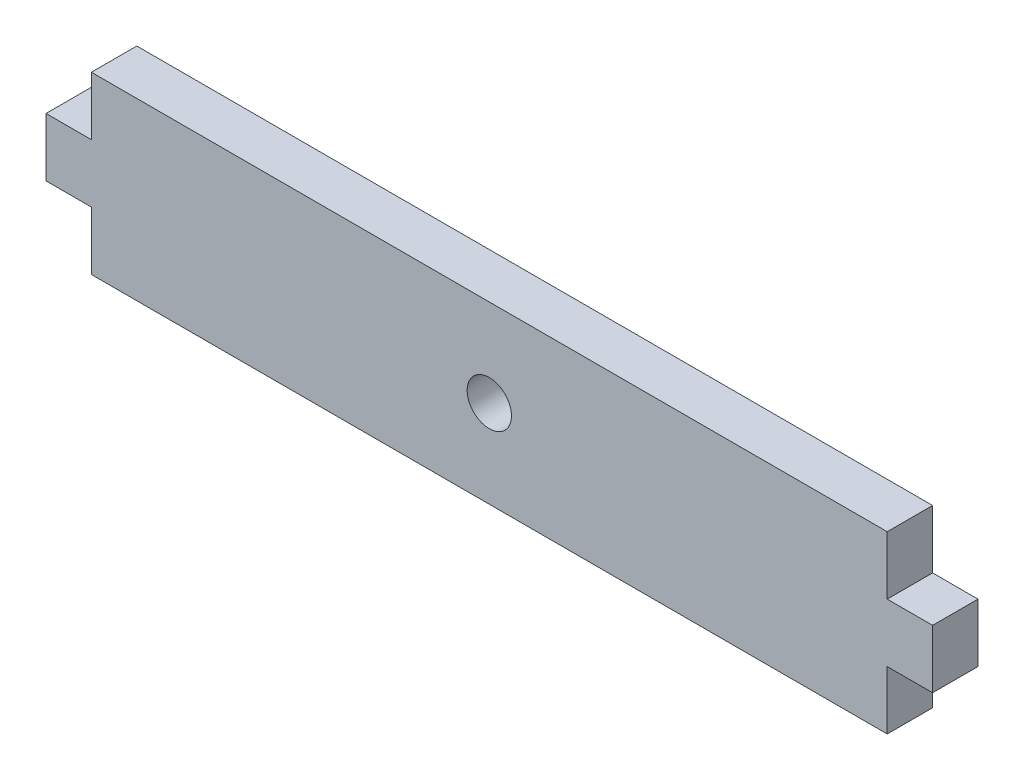
SolidWorks part; units mm, degrees
ref_plane "Front Plane" through (0, 0, 0) normal (0, 0, 1) x (1, 0, 0)
ref_plane "Top Plane" through (0, 0, 0) normal (0, 1, 0) x (1, 0, 0)
ref_plane "Right Plane" through (0, 0, 0) normal (1, 0, 0) x (0, 0, -1)
sketch "Sketch1" plane through (0, 0, 0) normal (0, 0, 1) x (1, 0, 0)
  line L0 (0, 8.718) -> (100, 8.718) construction
  line L1 (5.12, -1.1624) -> (94.88, -1.1624)
  line L2 (0, 5.4246) -> (0, 12.0115)
  line L3 (5.12, 18.5985) -> (94.88, 18.5985)
  line L4 (100, 5.4246) -> (100, 12.0115)
  line L6 (50, 18.5985) -> (50, -1.1624) construction
  line L7 (0, 12.0115) -> (5.12, 12.0115)
  line L8 (5.12, 18.5985) -> (5.12, 12.0115)
  line L11 (0, 5.4246) -> (5.12, 5.4246)
  line L12 (5.12, -1.1624) -> (5.12, 5.4246)
  line L15 (100, 12.0115) -> (94.88, 12.0115)
  line L16 (94.88, 18.5985) -> (94.88, 12.0115)
  line L19 (100, 5.4246) -> (94.88, 5.4246)
  line L20 (94.88, -1.1624) -> (94.88, 5.4246)
  circle A0 centre (50, 8.718) radius 2.5
  point P17 (50, 8.718)
  dimension "D3" = 5
  dimension "D1" = 100
  dimension "D2" = 5.12
extrude "Boss-Extrude1" add sketch "Sketch1" along normal blind 5.12
equation "\"D2@Sketch1\" = \"mdf@fmv1.assembly\""
equation "\"D1@Boss-Extrude1\"=\"mdf@fmv1.assembly\""
